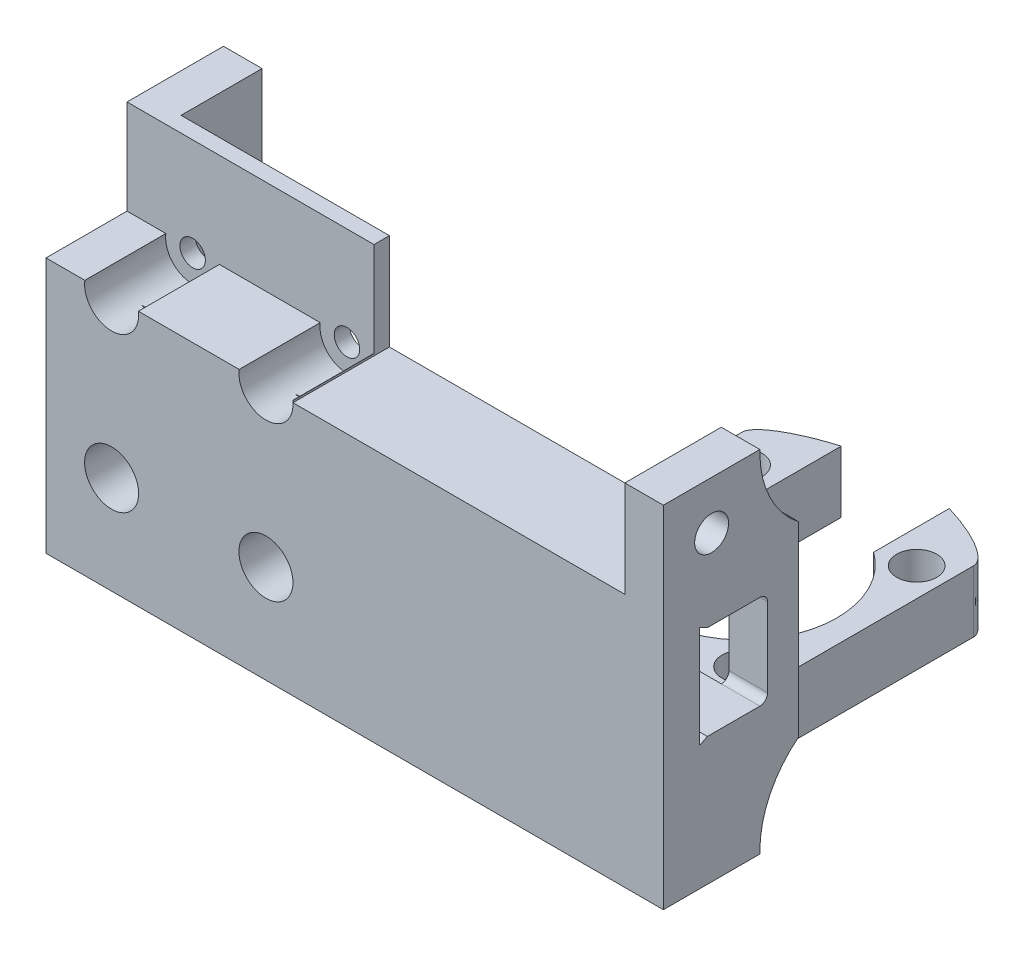
SolidWorks part; units mm, degrees
ref_plane "Front Plane" through (0, 0, 0) normal (0, 0, 1) x (1, 0, 0)
ref_plane "Top Plane" through (0, 0, 0) normal (0, 1, 0) x (1, 0, 0)
ref_plane "Right Plane" through (0, 0, 0) normal (1, 0, 0) x (0, 0, -1)
sketch "Sketch1" plane through (0, 0, 0) normal (0, 0, 1) x (1, 0, 0)
  line L1 (0, 0) -> (80, 0)
  line L2 (0, 0) -> (0, 45.4)
  line L3 (0, 45.4) -> (80, 45.4)
  line L4 (80, 0) -> (80, 45.4)
  line L5 (8.5, 32.7) -> (28.5, 32.7) construction
  line L6 (8.5, 32.7) -> (8.5, 12.7) construction
  line L7 (8.5, 12.7) -> (28.5, 12.7) construction
  line L8 (28.5, 32.7) -> (28.5, 12.7) construction
  circle A0 centre (8.5, 32.7) radius 1.65
  circle A1 centre (28.5, 32.7) radius 1.65
  circle A2 centre (28.5, 12.7) radius 1.65
  circle A3 centre (8.5, 12.7) radius 1.65
  dimension "D3" = 3.3
  dimension "D1" = 45.4
  dimension "D2" = 80
  dimension "D4" = 12.7
  dimension "D5" = 20
  dimension "D6" = 8.5
extrude "Boss-Extrude1" add sketch "Sketch1" along normal blind 12.5
sketch "Sketch2" plane through (0, 0, 0) normal (0, 0, -1) x (-1, 0, 0)
  line L0 (0, 0) -> (-80, 0) construction
  line L1 (0, 45.4) -> (-5, 45.4)
  line L2 (0, 45.4) -> (0, 0)
  line L3 (0, 0) -> (-5, 0)
  line L4 (-5, 45.4) -> (-5, 0)
  dimension "D1" = 5
extrude "Boss-Extrude2" add sketch "Sketch2" along normal blind 10.5
sketch "Sketch3" plane through (0, 0, 0) normal (0, 0, 1) x (1, 0, 0)
  line L0 (80, 0) -> (80, 45.4) construction
  line L1 (80, 28.8) -> (0, 28.8)
  line L2 (80, 28.8) -> (80, 16.6)
  line L3 (80, 16.6) -> (0, 16.6)
  line L4 (0, 28.8) -> (0, 16.6)
  line L5 (0, 0) -> (0, 45.4) construction
  line L6 (80, 22.7) -> (0, 22.7) construction
  point P10 (80, 22.7)
  dimension "D1" = 12.2
extrude "Cut-Extrude1" cut sketch "Sketch3" against normal through all and the other way blind 7.8
sketch "Sketch4" plane through (0, 0, 0) normal (0, 0, -1) x (-1, 0, 0)
  line L1 (-69.5, 0) -> (-39.5, 0)
  line L2 (-69.5, 0) -> (-69.5, 8)
  line L3 (-69.5, 8) -> (-39.5, 8)
  line L4 (-39.5, 0) -> (-39.5, 8)
  line L7 (-5, 0) -> (-80, 0) construction
  dimension "D1" = 8
  dimension "D2" = 30
  dimension "D3" = 39.5
extrude "Boss-Extrude3" add sketch "Sketch4" along normal blind 44.2
sketch "Sketch5" plane through (0, 8, 0) normal (0, 1, 0) x (1, 0, 0)
  line L0 (69.5, 44.2) -> (69.5, 0) construction
  line L1 (80, 0) -> (5, 0) construction
  circle A0 centre (54.4956, 23.5) radius 12
  dimension "D1" = 24
  dimension "D2" = 15.0044
  dimension "D3" = 23.5
extrude "Cut-Extrude2" cut sketch "Sketch5" against normal blind 45
sketch "Sketch6" plane through (0, 16.6, 0) normal (0, -1, 0) x (1, 0, 0)
  circle A3 centre (54.4956, -39.2013) radius 2.6
  circle A4 centre (65.8093, -34.515) radius 2.6
  circle A5 centre (43.1819, -34.515) radius 2.6
  circle A6 centre (43.1819, -11.8876) radius 2.6
  circle A7 centre (65.8093, -11.8876) radius 2.6
  dimension "D1" = 5.2
extrude "Cut-Extrude3" cut sketch "Sketch6" against normal through all both and the other way through all
fillet "Fillet1" radius 6 2 edges at (39.5, 4, -44.2) (69.5, 4, -44.2) second distance 15 conic rho 0.3 first distance on face at (39.5, 4, -22.1) first distance on face at (69.5, 4, -22.1)
sketch "Sketch8" plane through (0, 0, 12.5) normal (0, 0, 1) x (1, 0, 0)
  circle A0 centre (8.5, 32.7) radius 3.5
  circle A1 centre (28.5, 32.7) radius 3.5
  circle A2 centre (8.5, 12.7) radius 3.5
  circle A3 centre (28.5, 12.7) radius 3.5
  dimension "D1" = 7
extrude "Cut-Extrude5" cut sketch "Sketch8" against normal offset from surface (10.5 mm away) 2 up to face at (10.15, 12.7, 0)
sketch "Sketch12" plane through (0, 0, 12.5) normal (0, 0, 1) x (1, 0, 0)
  line L0 (80, 45.4) -> (0, 45.4) construction
  line L5 (0, 45.4) -> (45, 45.4)
  line L6 (0, 45.4) -> (0, 33.15)
  line L7 (0, 33.15) -> (45, 33.15)
  line L8 (45, 45.4) -> (45, 33.15)
  line L9 (0, 45.4) -> (0, 0) construction
  dimension "D1" = 12.25
  dimension "D2" = 45
extrude "Cut-Extrude8" cut sketch "Sketch12" against normal offset from surface (10.5 mm away) 2 up to face at (10.15, 32.7, 0)
sketch "Sketch13" plane through (0, 8, 0) normal (0, 1, 0) x (1, 0, 0)
  line L1 (61.4956, 50.8384) -> (47.4956, 50.8384)
  line L2 (61.4956, 50.8384) -> (61.4956, 27.5643)
  line L3 (61.4956, 27.5643) -> (47.4956, 27.5643)
  line L4 (47.4956, 50.8384) -> (47.4956, 27.5643)
  line L5 (61.4956, 50.8384) -> (47.4956, 27.5643) construction
  line L6 (61.4956, 27.5643) -> (47.4956, 50.8384) construction
  point P0 (54.4956, 39.2013)
  dimension "D1" = 14
extrude "Cut-Extrude10" cut sketch "Sketch13" against normal blind 10
sketch "Sketch14" plane through (0, 0, 0) normal (0, 0, -1) x (-1, 0, 0)
  line L1 (-80, 28.8) -> (0, 28.8)
  line L2 (-80, 28.8) -> (-80, 16.6)
  line L3 (-80, 16.6) -> (0, 16.6)
  line L4 (0, 28.8) -> (0, 16.6)
extrude "Boss-Extrude5" [suppressed] add sketch "Sketch14" against normal blind 0.5
sketch "Sketch15" plane through (0, 8, 0) normal (0, 1, 0) x (1, 0, 0)
  circle A0 centre (54.4956, 7.2013) radius 2.75
  point P2 (54.4956, 7.2013)
  dimension "D1" = 5.5
extrude "Boss-Extrude6" add sketch "Sketch15" along normal blind 2
sketch "Sketch16" plane through (0, 45.4, 0) normal (0, 1, 0) x (1, 0, 0)
  line L0 (39.5, 0) -> (69.5, 0) construction
  line L1 (75, 0) -> (32, 0)
  line L2 (75, 0) -> (75, -12.5)
  line L3 (75, -12.5) -> (32, -12.5)
  line L4 (32, 0) -> (32, -12.5)
  line L5 (80, -12.5) -> (45, -12.5) construction
  line L6 (80, -12.5) -> (80, 0) construction
  dimension "D1" = 32
  dimension "D2" = 5
extrude "Cut-Extrude11" cut sketch "Sketch16" against normal blind 12.5
sketch "Sketch17" plane through (80, 0, 0) normal (1, 0, 0) x (0, 0, -1)
  line L0 (-12.5, 45.4) -> (0, 45.4) construction
  line L1 (-6.25, 45.4) -> (-6.25, 28.8) construction
  line L2 (-7.8, 28.8) -> (0, 28.8) construction
  circle A0 centre (-6.25, 39.15) radius 2.2
  dimension "D1" = 4.4
  dimension "D2" = 6.25
extrude "Cut-Extrude12" cut sketch "Sketch17" against normal blind 10
sketch "Sketch18" plane through (80, 0, 0) normal (1, 0, 0) x (0, 0, -1)
  line L0 (-7.8, 28.8) -> (-6.8, 28.8)
  line L1 (-7.8, 28.8) -> (0, 28.8) construction
  line L2 (-6.8, 28.8) -> (-7.8, 29.3)
  line L3 (-7.8, 29.3) -> (-7.8, 28.8)
  line L4 (-7.8, 16.6) -> (-7.8, 16.1)
  line L5 (-7.8, 16.1) -> (-6.8, 16.6)
  line L6 (-7.8, 16.6) -> (0, 16.6) construction
  line L7 (-6.8, 16.6) -> (-7.8, 16.6)
  dimension "D1" = 0.5
  dimension "D2" = 1
  dimension "D3" = 1
  dimension "D4" = 0.5
extrude "Cut-Extrude13" cut sketch "Sketch18" against normal through all
sketch "Sketch19" plane through (0, 0, 0) normal (0, 0, -1) x (-1, 0, 0)
  line L0 (-80, 0) -> (-80, 16.6) construction
  line L1 (-75, 34.8) -> (-80, 34.8)
  line L2 (-75, 34.8) -> (-75, 10.6)
  line L3 (-75, 10.6) -> (-80, 10.6)
  line L4 (-80, 34.8) -> (-80, 10.6)
  line L5 (-5, 16.6) -> (-80, 16.6) construction
  line L6 (-80, 28.8) -> (-5, 28.8) construction
  line L7 (-75, 32.9) -> (-75, 45.4) construction
  dimension "D1" = 6
  dimension "D2" = 6
extrude "Boss-Extrude7" add sketch "Sketch19" along normal blind 5
sketch "Sketch20" plane through (80, 0, 0) normal (1, 0, 0) x (0, 0, -1)
  line L0 (0, 28.8) -> (0, 16.6)
  line L1 (0, 28.8) -> (1, 28.8)
  line L2 (0, 16.6) -> (1, 16.6)
  line L3 (1, 28.8) -> (1, 16.6)
  dimension "D1" = 1
extrude "Cut-Extrude14" cut sketch "Sketch20" against normal through all
sketch "Sketch21" plane through (0, 16.6, 0) normal (0, 1, 0) x (1, 0, 0)
  line L0 (5, 0) -> (5, 10.5) construction
  line L1 (0, 10.5) -> (5, 10.5)
  line L2 (0, 10.5) -> (0, 1)
  line L3 (0, 1) -> (5, 1)
  line L4 (5, 10.5) -> (5, 1)
  dimension "D1" = 9.5
extrude "Boss-Extrude8" add sketch "Sketch21" along normal up to surface (12.2 mm away) up to face at (40, 28.8, -1.175)
fillet "Fillet2" radius 1 4 edges at (77.5, 16.6, -1) (77.5, 28.8, -1) (2.5, 16.6, -1) (2.5, 28.8, -1)
fillet "Fillet3" radius 13 2 edges at (77.5, 10.6, 0) (77.5, 34.8, 0)
chamfer "Chamfer1" distance 2 angle 45 1 edges at (54.4956, 10, -4.4513)
